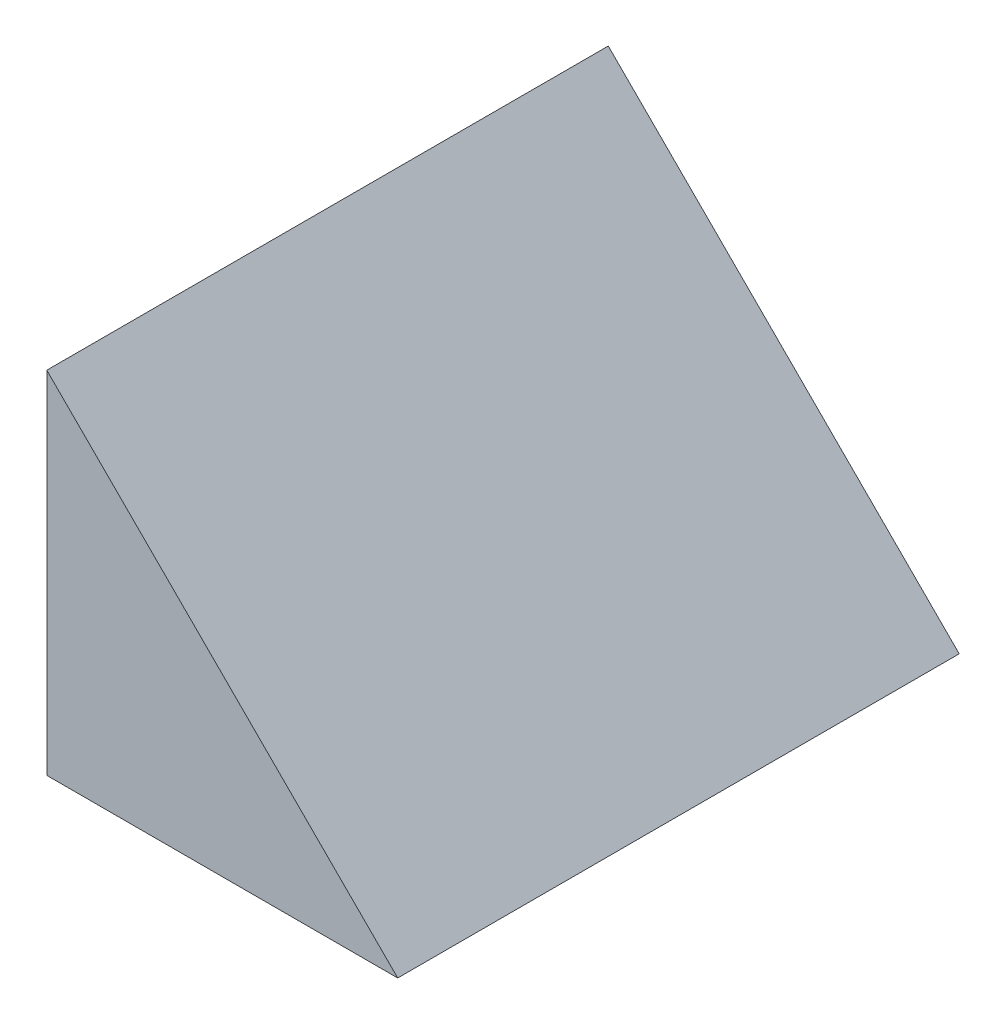
SolidWorks part; units mm, degrees
ref_plane "Front Plane" through (0, 0, 0) normal (0, 0, 1) x (1, 0, 0)
ref_plane "Top Plane" through (0, 0, 0) normal (0, 1, 0) x (1, 0, 0)
ref_plane "Right Plane" through (0, 0, 0) normal (1, 0, 0) x (0, 0, -1)
sketch "Sketch1" plane through (0, 0, 0) normal (0, 0, 1) x (1, 0, 0)
  line L0 (0, 0) -> (0, 0.25)
  line L1 (0, 0) -> (0.25, 0)
  line L5 (0, 0.25) -> (0.25, 0)
  dimension "D1" = 0.25
  dimension "D2" = 0.25
extrude "Boss-Extrude1" add sketch "Sketch1" along normal blind 0.4
equation "\"t\"= 0.25'thickness of the sheets"
equation "\"t_cf\" = 0.115'thickness of single carbon fiber layer"
equation "\"t_kapton\" = 0.025'thickness of single Kapton flex layer"
equation "\"t_fr4\" = 0.1'thickness of FR4 with copper layer"
equation "\"joint_flex\"= 0.1'Width of flextures gap"
equation "\"joint_flex_eff\"= 0.02'Width of flecture after castelation"
equation "\"joint_fold\"= 0.2'Width of folding joints for 90deg fold"
equation "\"gap_tolerance\"= 0.002'Width to have interfecence fit between carbon fiber inserts"
equation "\"assemble_angle\"= 90'Angle of assembly parts"
equation "\"link_lift\"= 0.5'Actuation linkage amplification for the lift motion"
equation "\"link_swing\"= 0.45'Actuation linkage amplification for the swing motion"
equation "\"D1@Boss-Extrude1\"=\"joint_fold\""
equation "\"D1@Sketch1\"=\"t\""
equation "\"D2@Sketch1\"=\"t\""
